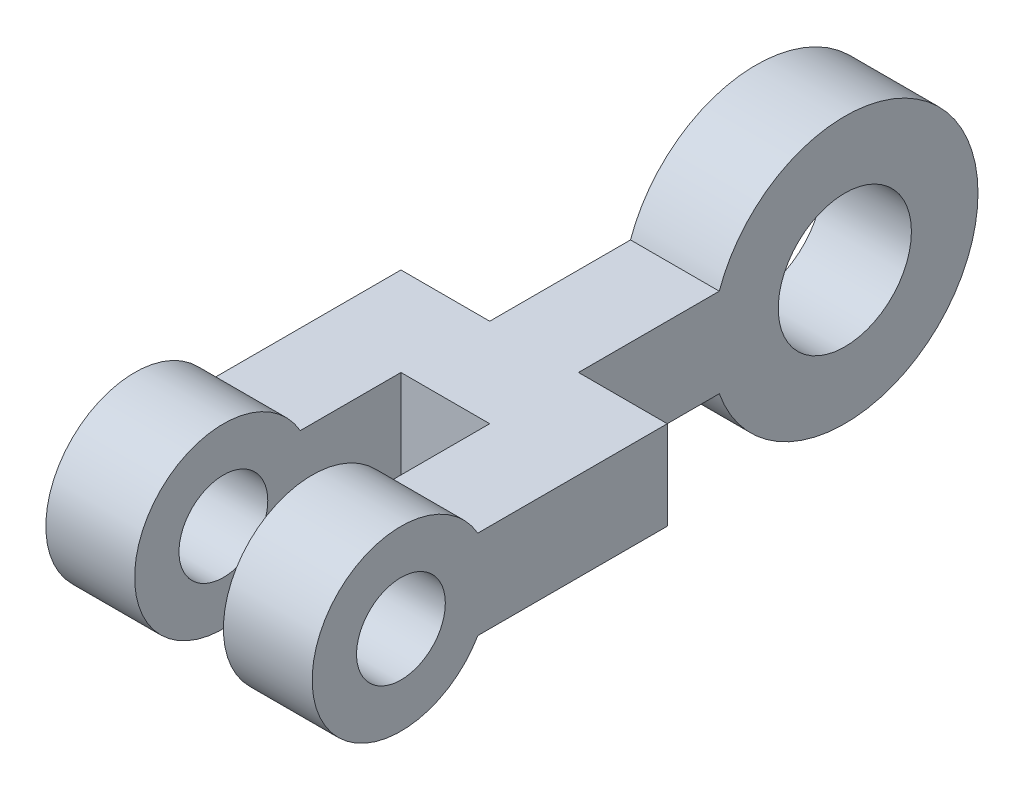
SolidWorks part; units mm, degrees
ref_plane "Front Plane" through (0, 0, 0) normal (0, 0, 1) x (1, 0, 0)
ref_plane "Top Plane" through (0, 0, 0) normal (0, 1, 0) x (1, 0, 0)
ref_plane "Right Plane" through (0, 0, 0) normal (1, 0, 0) x (0, 0, -1)
sketch "Sketch1" plane through (0, 0, 0) normal (1, 0, 0) x (0, 0, -1)
  line L0 (10.9985, -6.35) -> (58.2395, -6.35)
  line L1 (58.2395, 6.35) -> (10.9985, 6.35)
  line L2 (38.1, 6.35) -> (38.1, -6.35)
  line L3 (25.4, 6.35) -> (25.4, -6.35)
  circle A0 centre (0, 0) radius 6.35
  circle A1 centre (0, 0) radius 12.7
  circle A2 centre (76.2, 0) radius 19.05
  circle A3 centre (76.2, 0) radius 9.525
  dimension "D1" = 12.7
  dimension "D2" = 25.4
  dimension "D4" = 38.1
  dimension "D5" = 19.05
  dimension "D3" = 76.2
  dimension "D6" = 12.7
  dimension "D7" = 25.4
  dimension "D8" = 12.7
extrude "Boss-Extrude1" add sketch "Sketch1" along normal mid plane 12.7 contours A2 A3 | A2 L1 L2 L0 region at (0, 0, -47.8071) region at (0, 0, -57.6888)
extrude "Boss-Extrude2" add sketch "Sketch1<3>" along normal mid plane 38.1 contours L1 L3 L0 L2 region at (0, 0, -31.75)
sketch "Sketch1<3>" plane through (0, 0, 0) normal (1, 0, 0) x (0, 0, -1) same geometry as "Sketch1"
extrude "Boss-Extrude3" add sketch "Sketch1<4>" along normal blind 12.7 from offset 6.35 separate body contours A1 L0 L3 L1 | A1 A0 region at (0, 0, -18.765) region at (0, 0, 12.3408)
sketch "Sketch1<4>" plane through (0, 0, 0) normal (1, 0, 0) x (0, 0, -1) same geometry as "Sketch1"
mirror "Mirror2" about plane through (0, 0, 0) normal (1, 0, 0) of "Boss-Extrude3"
combine bodies "Combine1" operation type add bodies to combine 103 104
